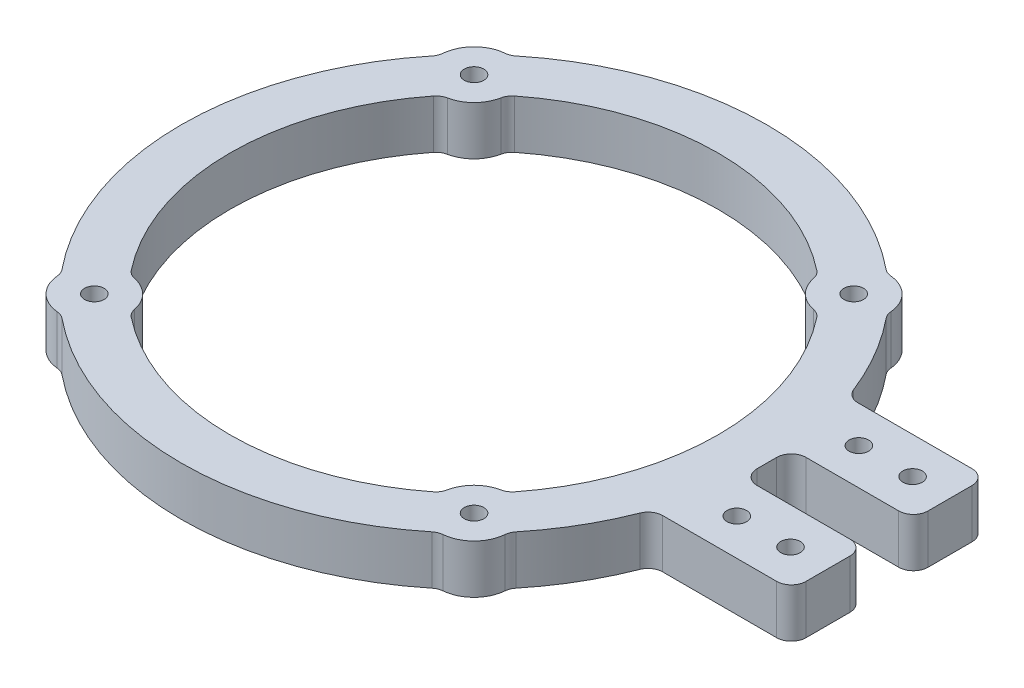
SolidWorks part; units mm, degrees
material "1060 Alloy"
ref_plane "Front Plane" through (0, 0, 0) normal (0, 0, 1) x (1, 0, 0)
ref_plane "Top Plane" through (0, 0, 0) normal (0, 1, 0) x (1, 0, 0)
ref_plane "Right Plane" through (0, 0, 0) normal (1, 0, 0) x (0, 0, -1)
sketch "Sketch1" plane through (0, 0, 0) normal (0, 1, 0) x (1, 0, 0)
  line L0 (0, -50) -> (0, -60) construction
  line L1 (0, 0) -> (0, -50) construction
  line L2 (56.5685, -20) -> (85, -20)
  line L3 (85, -20) -> (85, -5)
  line L4 (85, -5) -> (60, -5)
  line L5 (60, -5) -> (60, 5)
  line L6 (60, 5) -> (85, 5)
  line L7 (85, 5) -> (85, 20)
  line L8 (85, 20) -> (56.5685, 20)
  circle A0 centre (0, 0) radius 50
  circle A1 centre (0, 0) radius 60 construction
  arc A2 (56.5685, 20) -> (56.5685, -20) centre (0, 0) ccw
  dimension "D1" = 100
  dimension "D2" = 10
  dimension "D3" = 10
  dimension "D4" = 15
  dimension "D6" = 25
extrude "Boss-Extrude1" add sketch "Sketch1" along normal blind 10
sketch "Sketch3" plane through (0, 10, 0) normal (0, 1, 0) x (1, 0, 0)
  line L0 (38.8909, 38.8909) -> (38.8909, -38.8909) construction
  line L1 (60, -5) -> (60, 5) construction
  circle A0 centre (0, 0) radius 55 construction
  circle A1 centre (38.8909, -38.8909) radius 7
  circle A2 centre (-38.8909, -38.8909) radius 7
  circle A3 centre (-38.8909, 38.8909) radius 7
  circle A4 centre (38.8909, 38.8909) radius 7
  point P14 (0, 0)
  dimension "D1" = 110
  dimension "D2" = 14
  dimension "D3" = 4
extrude "Boss-Extrude2" add sketch "Sketch3" against normal up to surface (10 mm away) up to face at (57.0711, 0, 0)
sketch "Sketch4" plane through (0, 10, 0) normal (0, 1, 0) x (1, 0, 0)
  circle A0 centre (38.8909, -38.8909) radius 2
  circle A1 centre (-38.8909, -38.8909) radius 2
  circle A2 centre (-38.8909, 38.8909) radius 2
  circle A3 centre (38.8909, 38.8909) radius 2
  point P12 (0, 0)
  dimension "D1" = 4
  dimension "D2" = 4
extrude "Cut-Extrude1" cut sketch "Sketch4" against normal blind 10
fillet "Fillet1" radius 3 24 edges at (85, 5, -20) (85, 5, -5) (85, 5, 5) (85, 5, 20) (38.5003, 5, 31.9018) (31.9018, 5, 38.5003) (38.5003, 5, -31.9018) (31.9018, 5, -38.5003) (-38.5003, 5, -31.9018) (-31.9018, 5, -38.5003) (-45.887, 5, -38.6573) (-38.6573, 5, -45.887) (38.6573, 5, -45.887) (45.887, 5, -38.6573) (-31.9018, 5, 38.5003) (-38.5003, 5, 31.9018) (-45.887, 5, 38.6573) (-38.6573, 5, 45.887) (38.6573, 5, 45.887) (45.887, 5, 38.6573) (56.5685, 5, 20) (56.5685, 5, -20) (60, 5, 5) (60, 5, -5)
sketch "Sketch5" plane through (0, 10, 0) normal (0, 1, 0) x (1, 0, 0)
  line L0 (58.6515, 20) -> (85, 5) construction
  line L1 (85, 20) -> (58.6515, 5) construction
  line L2 (58.6515, 5) -> (85, 5) construction
  line L3 (58.6515, 20) -> (58.6515, 5) construction
  line L4 (66.3258, 12.5) -> (77.3258, 12.5) construction
  line L5 (58.6515, 20) -> (85, 20) construction
  line L6 (85, 20) -> (85, 5) construction
  line L7 (63, 5) -> (82, 5) construction
  line L8 (85, 8) -> (85, 17) construction
  line L9 (58.6515, -5) -> (85, -20) construction
  line L10 (85, -5) -> (58.6515, -20) construction
  line L11 (58.6515, -20) -> (85, -20) construction
  line L12 (58.6515, -5) -> (58.6515, -20) construction
  line L13 (66.3258, -12.5) -> (77.3258, -12.5) construction
  line L14 (58.6515, -5) -> (85, -5) construction
  line L15 (85, -5) -> (85, -20) construction
  line L16 (82, -5) -> (63, -5) construction
  line L17 (58.6515, -20) -> (82, -20) construction
  circle A0 centre (66.3258, 12.5) radius 2
  circle A1 centre (77.3258, 12.5) radius 2
  circle A2 centre (66.3258, -12.5) radius 2
  circle A3 centre (77.3258, -12.5) radius 2
  point P11 (71.8258, 12.5)
  point P21 (71.8258, -12.5)
  dimension "D2" = 4
  dimension "D3" = 4
  dimension "D5" = 4
  dimension "D6" = 4
  dimension "D1" = 11
  dimension "D4" = 11
extrude "Cut-Extrude2" cut sketch "Sketch5" against normal blind 10
